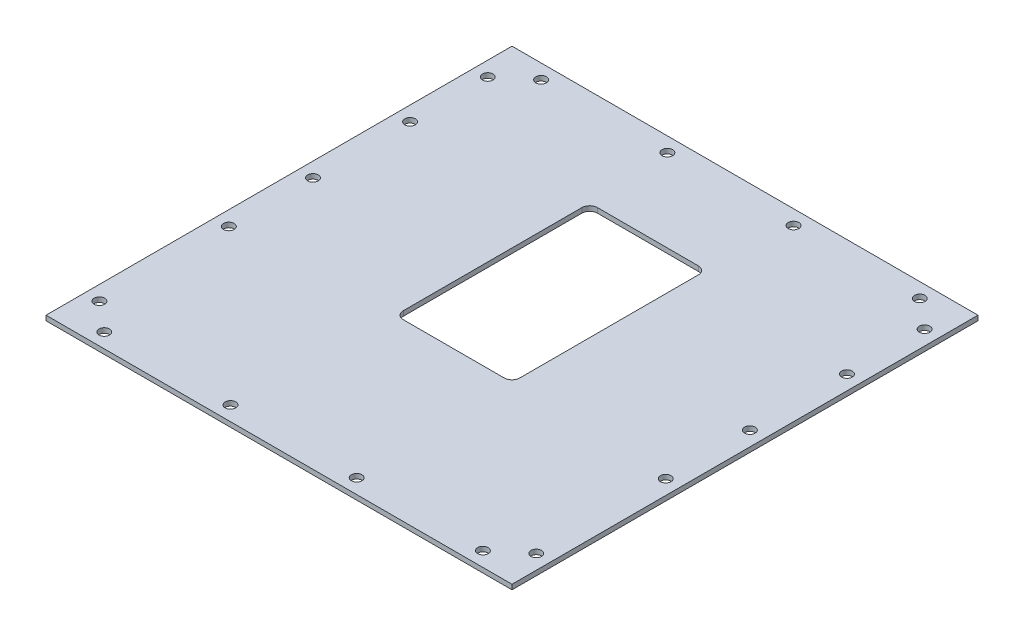
SolidWorks part; units mm, degrees
ref_plane "Front Plane" through (0, 0, 0) normal (0, 0, 1) x (1, 0, 0)
ref_plane "Top Plane" through (0, 0, 0) normal (0, 1, 0) x (1, 0, 0)
ref_plane "Right Plane" through (0, 0, 0) normal (1, 0, 0) x (0, 0, -1)
sketch "Sketch2" plane through (0, 0, 0) normal (0, 1, 0) x (1, 0, 0)
  line L0 (0, 0) -> (152.4, 0)
  line L1 (152.4, 0) -> (152.4, 152.4)
  line L2 (152.4, 152.4) -> (0, 152.4)
  line L3 (0, 152.4) -> (0, 0)
  dimension "D1" = 152.4
  dimension "D2" = 152.4
extrude "Boss-Extrude1" add sketch "Sketch2" along normal blind 1.5875
sketch "Sketch3" plane through (0, 1.5875, 0) normal (0, 1, 0) x (1, 0, 0)
  line L0 (0, 152.4) -> (4.7625, 152.4)
  line L1 (152.4, 152.4) -> (0, 152.4) construction
  line L2 (4.7625, 152.4) -> (4.7625, 0)
  line L3 (0, 0) -> (152.4, 0) construction
  line L4 (0, 152.4) -> (0, 147.6375)
  line L5 (0, 152.4) -> (0, 0) construction
  line L6 (0, 147.6375) -> (152.4, 147.6375)
  line L7 (152.4, 0) -> (152.4, 152.4) construction
  line L8 (152.4, 152.4) -> (147.6375, 152.4)
  line L9 (147.6375, 152.4) -> (147.6375, 0)
  line L10 (152.4, 0) -> (152.4, 4.7625)
  line L11 (152.4, 4.7625) -> (0, 4.7625)
  point P21 (4.7625, 139.7)
  point P23 (14.2875, 147.6375)
  point P24 (147.6375, 139.7)
  point P25 (138.1125, 4.7625)
  point P26 (4.7625, 12.7)
  dimension "D1" = 4.7625
  dimension "D2" = 4.7625
  dimension "D3" = 4.7625
  dimension "D4" = 4.7625
  dimension "D5" = 12.7
  dimension "D6" = 14.2875
  dimension "D7" = 12.7
  dimension "D8" = 14.2875
  dimension "D9" = 12.7
sketch "Sketch4" plane through (0, 1.5875, 0) normal (0, 1, 0) x (1, 0, 0)
  point P0 (14.2875, 147.6375)
  point P3 (147.6375, 139.7)
  point P6 (138.1125, 4.7625)
  point P9 (4.7625, 12.7)
sketch "Sketch6" plane through (0, 1.5875, 0) normal (0, 1, 0) x (1, 0, 0)
  line L0 (152.4, 4.7625) -> (0, 4.7625) construction
  line L1 (0, 152.4) -> (0, 0) construction
  point P0 (14.2875, 147.6375)
  point P3 (14.2875, 4.7625)
  dimension "D1" = 14.2875
hole_wizard "#5 Clearance Hole2" positions "Sketch6" profile "Sketch7" hole size "#5" standard "ANSI Inch" end condition through all
sketch "Sketch7" plane through (14.2875, 1.5875, -147.6375) normal (1, 0, 0) x (0, 0, 1)
  line L0 (0, 0) -> (0, 1.5875)
  line L1 (0, 1.5875) -> (1.7272, 1.5875)
  line L2 (1.7272, 1.5875) -> (1.7272, 0)
  line L5 (1.7272, 0) -> (0, 0)
  line L11 (0, -6.35) -> (0, 107.95) construction
  dimension "Thru Hole Dia." = 3.4544
  dimension "Thru Hole Depth" = 1.5875
sketch "Sketch8" plane through (0, 1.5875, 0) normal (0, 1, 0) x (1, 0, 0)
  point P0 (4.7625, 139.7)
  point P3 (147.6375, 139.7)
hole_wizard "#5 Clearance Hole3" positions "Sketch8" profile "Sketch9" hole size "#5" standard "ANSI Inch" end condition through all
sketch "Sketch9" plane through (4.7625, 1.5875, -139.7) normal (1, 0, 0) x (0, 0, 1)
  line L0 (0, 0) -> (0, 1.5875)
  line L1 (0, 1.5875) -> (1.7272, 1.5875)
  line L2 (1.7272, 1.5875) -> (1.7272, 0)
  line L5 (1.7272, 0) -> (0, 0)
  line L11 (0, -6.35) -> (0, 107.95) construction
  dimension "Thru Hole Dia." = 3.4544
  dimension "Thru Hole Depth" = 1.5875
pattern_linear "LPattern1" count 4 spacing 42.3333 along (0, 0, 1) skipping (1, 0) of "#5 Clearance Hole3"
pattern_linear "LPattern2" count 4 spacing 41.275 along (1, 0, 0) of "#5 Clearance Hole2"
sketch "Sketch10" plane through (0, 1.5875, 0) normal (0, 1, 0) x (1, 0, 0)
  line L0 (152.4, 0) -> (152.4, 152.4) construction
  line L1 (152.4, 152.4) -> (0, 152.4) construction
  line L2 (76.2, 152.4) -> (76.2, 0) construction
  line L3 (0, 0) -> (152.4, 0) construction
  point P0 (147.6375, 114.3)
  point P5 (147.6375, 82.55)
  point P10 (4.7625, 82.55)
  point P11 (4.7625, 114.3)
  dimension "D1" = 4.7625
  dimension "D2" = 38.1
  dimension "D3" = 31.75
hole_wizard "#5 Clearance Hole4" positions "Sketch10" profile "Sketch11" hole size "#5" standard "ANSI Inch"
sketch "Sketch11" plane through (147.6375, 1.5875, -114.3) normal (1, 0, 0) x (0, 0, 1)
  line L0 (0, 0) -> (0, 13.7378)
  line L1 (0, 13.7378) -> (1.7272, 12.7)
  line L2 (1.7272, 12.7) -> (1.7272, 0)
  line L5 (1.7272, 0) -> (0, 0)
  line L10 (0, 13.7378) -> (-1.7272, 12.7) construction
  line L11 (0, -6.35) -> (0, 107.95) construction
  dimension "Hole Dia." = 3.4544
  dimension "Hole Depth" = 12.7
  dimension "Drill Angle" = 118
sketch "Sketch12" plane through (0, 1.5875, 0) normal (0, 1, 0) x (1, 0, 0)
  line L10 (0, 152.4) -> (0, 0) construction
  line L11 (57.15, 120.65) -> (95.25, 120.65)
  line L12 (57.15, 120.65) -> (57.15, 57.15)
  line L13 (57.15, 57.15) -> (95.25, 57.15)
  line L14 (95.25, 120.65) -> (95.25, 57.15)
  line L15 (152.4, 152.4) -> (0, 152.4) construction
  line L16 (152.4, 0) -> (152.4, 152.4) construction
  dimension "D1" = 57.15
  dimension "D2" = 31.75
  dimension "D3" = 57.15
  dimension "D4" = 63.5
extrude "Cut-Extrude1" cut sketch "Sketch12" against normal blind 2.54 contours L14 L12 region at (76.2, 1.5875, -88.9)
fillet "Fillet2" radius 2.54 4 edges at (95.25, 0.7937, -57.15) (57.15, 0.7937, -57.15) (57.15, 0.7937, -120.65) (95.25, 0.7937, -120.65)
